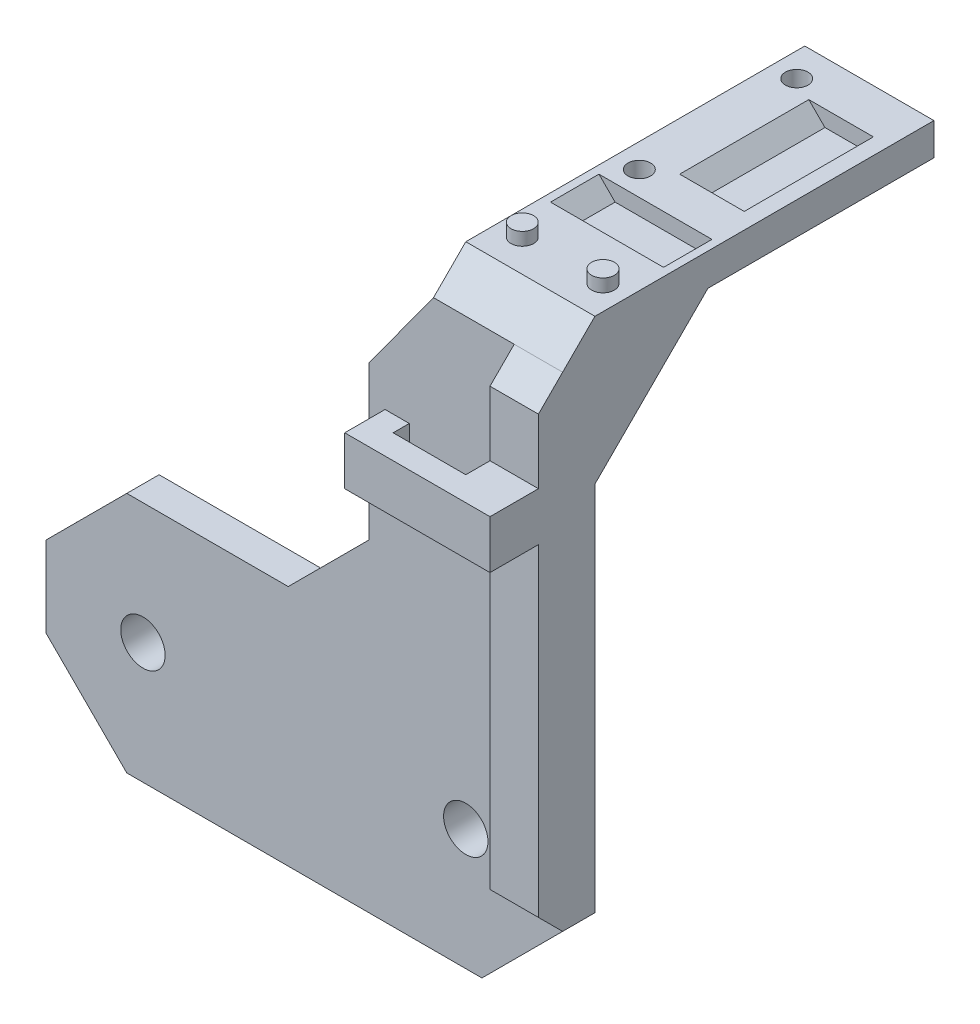
SolidWorks part; units mm, degrees
ref_plane "Front Plane" through (0, 0, 0) normal (0, 0, 1) x (1, 0, 0)
ref_plane "Top Plane" through (0, 0, 0) normal (0, 1, 0) x (1, 0, 0)
ref_plane "Right Plane" through (0, 0, 0) normal (1, 0, 0) x (0, 0, -1)
sketch "Sketch1" plane through (0, 0, 0) normal (0, 0, 1) x (1, 0, 0)
  line L1 (-12, 37) -> (12, 37)
  line L2 (-12, 37) -> (-12, -37)
  line L3 (-12, -37) -> (12, -37)
  line L4 (12, 37) -> (12, -37)
  line L5 (-12, 37) -> (12, -37) construction
  line L6 (-12, -37) -> (12, 37) construction
  point P0 (0, 0)
  dimension "D1" = 74
  dimension "D2" = 24
extrude "Boss-Extrude1" add sketch "Sketch1" along normal blind 4
sketch "Sketch3" plane through (0, 0, 0) normal (0, 0, 1) x (1, 0, 0)
  line L0 (12, -37) -> (12, 37) construction
  line L1 (-12, 37) -> (12, 37)
  line L2 (-12, 37) -> (-12, 33)
  line L3 (-12, 33) -> (12, 33)
  line L4 (12, 37) -> (12, 33)
  dimension "D1" = 4
extrude "Boss-Extrude2" add sketch "Sketch3" against normal blind 42
chamfer "Chamfer1" distance 14 angle 45 1 edges
chamfer "Chamfer2" distance 4 angle 45 1 edges at (0, 37, 4)
sketch "Sketch4" plane through (0, 37, 0) normal (0, 1, 0) x (1, 0, 0)
  line L0 (-12, 42) -> (-12, 0)
  line L1 (-12, 0) -> (-4, 0)
  line L2 (-12, 0) -> (12, 0) construction
  line L3 (-4, 0) -> (-4, 42)
  line L4 (12, 42) -> (-12, 42) construction
  line L5 (-4, 42) -> (-12, 42)
  line L6 (12, 0) -> (12, 42) construction
  line L12 (-35.2, 0) -> (35.2, 0) construction
  dimension "D1" = 16
extrude "Cut-Extrude3" cut sketch "Sketch4" against normal blind 30
sketch "Sketch5" plane through (0, 37, 0) normal (0, 1, 0) x (1, 0, 0)
  line L0 (12, 0) -> (12, 42) construction
  line L1 (-4, 0) -> (12, 0) construction
  line L2 (-4, 0) -> (-4, 42) construction
  circle A0 centre (-1, 4) radius 1.4
  circle A1 centre (9, 4) radius 1.4
  dimension "D1" = 2.8
  dimension "D2" = 2.8
  dimension "D3" = 3
  dimension "D4" = 4
  dimension "D5" = 3
  dimension "D6" = 4
extrude "Boss-Extrude3" add sketch "Sketch5" along normal blind 1.6
sketch "Sketch6" plane through (0, 37, 0) normal (0, 1, 0) x (1, 0, 0)
  line L0 (-4, 0) -> (-4, 42) construction
  line L1 (12, 42) -> (-4, 42) construction
  line L2 (-4, 0) -> (12, 0) construction
  circle A0 centre (-1, 18.5) radius 1.4
  circle A1 centre (-1, 38) radius 1.4
  point P6 (-4, 21)
  dimension "D1" = 2.8
  dimension "D2" = 2.8
  dimension "D3" = 3
  dimension "D4" = 3
  dimension "D5" = 4
  dimension "D6" = 18.5
extrude "Cut-Extrude4" cut sketch "Sketch6" against normal up to next
ref_plane "Plane1" through (0, 22, 0) normal (0, 1, 0) x (1, 0, 0)
sketch "Sketch7" plane through (0, 22, 0) normal (0, 1, 0) x (1, 0, 0)
  line L0 (12, -4) -> (12, -13)
  line L1 (12, -13) -> (-6, -13)
  line L2 (-6, -13) -> (-6, -8)
  line L3 (-6, -8) -> (-3, -8)
  line L4 (-3, -8) -> (-3, -10)
  line L5 (-3, -10) -> (6, -10)
  line L6 (6, -10) -> (6, -4)
  line L7 (12, -4) -> (-12, -4) construction
  line L8 (6, -4) -> (12, -4)
  dimension "D1" = 6
  dimension "D2" = 18
  dimension "D3" = 3
  dimension "D4" = 5
  dimension "D5" = 2
  dimension "D6" = 9
extrude "Boss-Extrude4" add sketch "Sketch7" against normal blind 6
sketch "Sketch9" plane through (0, 0, 0) normal (0, 0, 1) x (1, 0, 0)
  line L0 (-4, 37) -> (-4, 33)
  line L1 (12, 33) -> (-12, 33) construction
  line L2 (-4, 33) -> (-12, 22)
  line L3 (30.25, 22) -> (-30.25, 22) construction
  line L4 (-12, 22) -> (-12, 37)
  line L5 (-12, 37) -> (-4, 37)
extrude "Cut-Extrude6" cut sketch "Sketch9" along normal up to next
sketch "Sketch11" plane through (0, 0, 0) normal (0, 0, 1) x (1, 0, 0)
  line L1 (-12, -37) -> (-52, -37)
  line L2 (-12, -37) -> (-12, -7)
  line L3 (-12, -7) -> (-52, -7)
  line L4 (-52, -37) -> (-52, -7)
  dimension "D1" = 30
  dimension "D2" = 40
extrude "Boss-Extrude6" add sketch "Sketch11" along normal blind 4
sketch "Sketch2" plane through (0, 0, 0) normal (0, 0, 1) x (1, 0, 0)
  line L3 (0, -30.25) -> (0, 30.25) construction
  line L4 (-52, -37) -> (12, -37) construction
  line L5 (-52, -37) -> (12, -37) construction
  line L6 (-52, -7) -> (-52, -37) construction
  circle A0 centre (0, -22) radius 2.75
  circle A1 centre (-40, -22) radius 2.75
  dimension "D1" = 5.5
  dimension "D2" = 15
  dimension "D3" = 5.5
  dimension "D4" = 15
  dimension "D5" = 12
extrude "Cut-Extrude2" cut sketch "Sketch2" along normal up to next
chamfer "Chamfer3" distance 10 angle 45 4 edges at (-52, -37, 2) (-52, -7, 2) (12, -37, 2)
sketch "Sketch12" plane through (12, 0, 0) normal (1, 0, 0) x (0, 0, -1)
  line L1 (-4, 33) -> (-7, 33)
  line L2 (-4, 33) -> (-4, -27)
  line L3 (-4, -27) -> (-7, -27)
  line L4 (-7, 33) -> (-7, -27)
  dimension "D1" = 60
  dimension "D2" = 3
extrude "Boss-Extrude7" add sketch "Sketch12" against normal blind 6
chamfer "Chamfer4" distance 3 angle 45 2 edges at (9, 33, 7) (9, -27, 7)
sketch "Sketch13" plane through (0, 37, 0) normal (0, 1, 0) x (1, 0, 0)
  line L0 (12, 0) -> (12, 42) construction
  line L1 (4, 36.5) -> (8, 36.5)
  line L2 (4, 36.5) -> (4, 20.5)
  line L3 (4, 20.5) -> (8, 20.5)
  line L4 (8, 36.5) -> (8, 20.5)
  line L5 (9, 15.5) -> (-1, 15.5)
  line L6 (9, 15.5) -> (9, 9.5)
  line L7 (9, 9.5) -> (-1, 9.5)
  line L8 (-1, 15.5) -> (-1, 9.5)
  line L9 (12, 42) -> (-4, 42) construction
  line L10 (-35.2, 0) -> (35.2, 0) construction
  line L11 (-4, 0) -> (-4, 42) construction
  dimension "D1" = 4
  dimension "D2" = 4
  dimension "D3" = 16
  dimension "D4" = 5.5
  dimension "D5" = 6
  dimension "D6" = 9.5
  dimension "D7" = 10
  dimension "D8" = 3
extrude "Cut-Extrude7" cut sketch "Sketch13" against normal blind 2
chamfer "Chamfer5" distance 2 angle 45 4 edges at (4, 37, -28.5) (-1, 37, -12.5) (9, 37, -12.5) (8, 37, -28.5)
